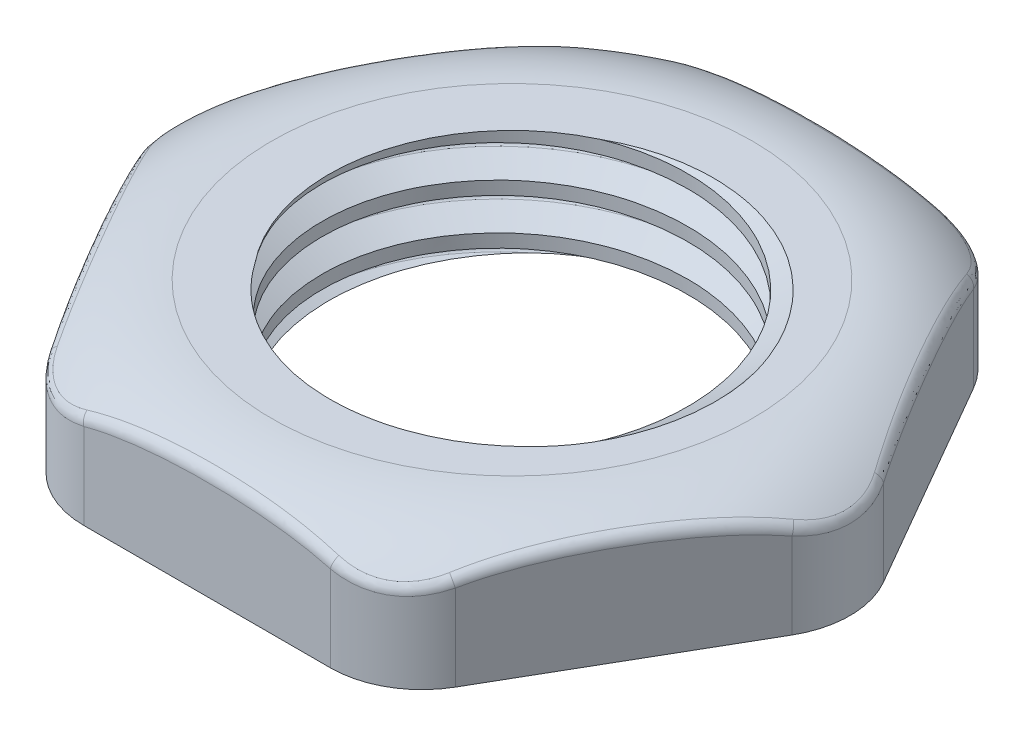
SolidWorks part; units mm, degrees
ref_plane "Face" through (0, 0, 0) normal (0, 0, 1) x (1, 0, 0)
ref_plane "Dessus" through (0, 0, 0) normal (0, 1, 0) x (1, 0, 0)
ref_plane "Droite" through (0, 0, 0) normal (1, 0, 0) x (0, 0, -1)
sketch "Esquisse1" plane through (0, 0, 0) normal (0, 1, 0) x (1, 0, 0)
  line L1 (2.8868, 5) -> (-2.8868, 5)
  line L2 (-2.8868, 5) -> (-5.7735, 0)
  line L3 (-5.7735, 0) -> (-2.8868, -5)
  line L4 (-2.8868, -5) -> (2.8868, -5)
  line L5 (2.8868, -5) -> (5.7735, 0)
  line L6 (5.7735, 0) -> (2.8868, 5)
  circle A0 centre (0, 0) radius 5 construction
  circle A1 centre (0, 0) radius 3
  dimension "D1" = 10
  dimension "D2" = 6
extrude "Boss.-Extru.1" add sketch "Esquisse1" along normal blind 2
sketch "Esquisse2" plane through (0, 0, 0) normal (0, 0, 1) x (1, 0, 0)
  line L0 (-2.7664, 2.8028) -> (-3.375, 2.4514)
  line L1 (-3.375, 2.3514) -> (-2.7664, 2)
  line L2 (-2.7664, 2) -> (-2.7664, 2.8028)
  line L3 (5.7735, 2) -> (2.8868, 2) construction
  arc A0 (-3.375, 2.4514) -> (-3.375, 2.3514) centre (-3.3461, 2.4014) ccw
  dimension "D2" = 0.1
  dimension "D1" = 60
  dimension "D3" = 3.375
  dimension "D4" = 2.7664
sketch "Esquisse3" plane through (0, 2, 0) normal (0, 1, 0) x (1, 0, 0)
  circle A0 centre (0, 0) radius 3 construction
  circle A1 centre (0, 0) radius 3
curve "Hélice/Spirale1" pitch 0.75 height 6.9375 turns 9.25
sweep "Enlèvement de matière-Balayage1" cut profiles "Esquisse2" path "Hélice/Spirale1"
fillet "Congé1" radius 1.5 6 edges at (-5.7735, 1, 0) (-2.8868, 1, 5) (2.8868, 1, 5) (5.7735, 1, 0) (2.8868, 1, -5) (-2.8868, 1, -5)
sketch "Esquisse4" plane through (0, 0, 0) normal (0, 0, 1) x (1, 0, 0)
  line L0 (-5.5415, 1.4) -> (-5.5415, 2)
  line L1 (-5.5415, 2) -> (-5.5415, 0) construction
  line L2 (-5.3405, 2) -> (-5.5415, 2) construction
  line L3 (-5.5415, 2) -> (-3.9415, 2)
  line L4 (-5.3405, 2) -> (-3.3198, 2) construction
  line L5 (-5.3405, 0) -> (-3.3198, 0) construction
  line L6 (0, 0) -> (0, 2.2675) construction
  arc A0 (-3.9415, 2) -> (-5.5415, 1.4) centre (-3.9415, -0.4333) ccw
  dimension "D1" = 1.4
  dimension "D2" = 1.6
revolve "Enlèvement de matière-Révolution1" cut sketch "Esquisse4" angle 360 about L6
fillet "Congé2" radius 0.2 12 edges at (-4.4051, 1.7566, -2.3701) (-5.5361, 1.4034, -0.1264) (-4.2551, 1.7566, 2.6299) (-2.8776, 1.4034, 4.7312) (1.2135, -2.5481, 5) (2.6586, 1.4034, 4.8576) (4.4051, 1.7566, 2.3701) (5.5361, 1.4034, 0.1264) (4.2551, 1.7566, -2.6299) (2.8776, 1.4034, -4.7312) (-1.2135, -2.5481, -5) (-2.6586, 1.4034, -4.8576)
